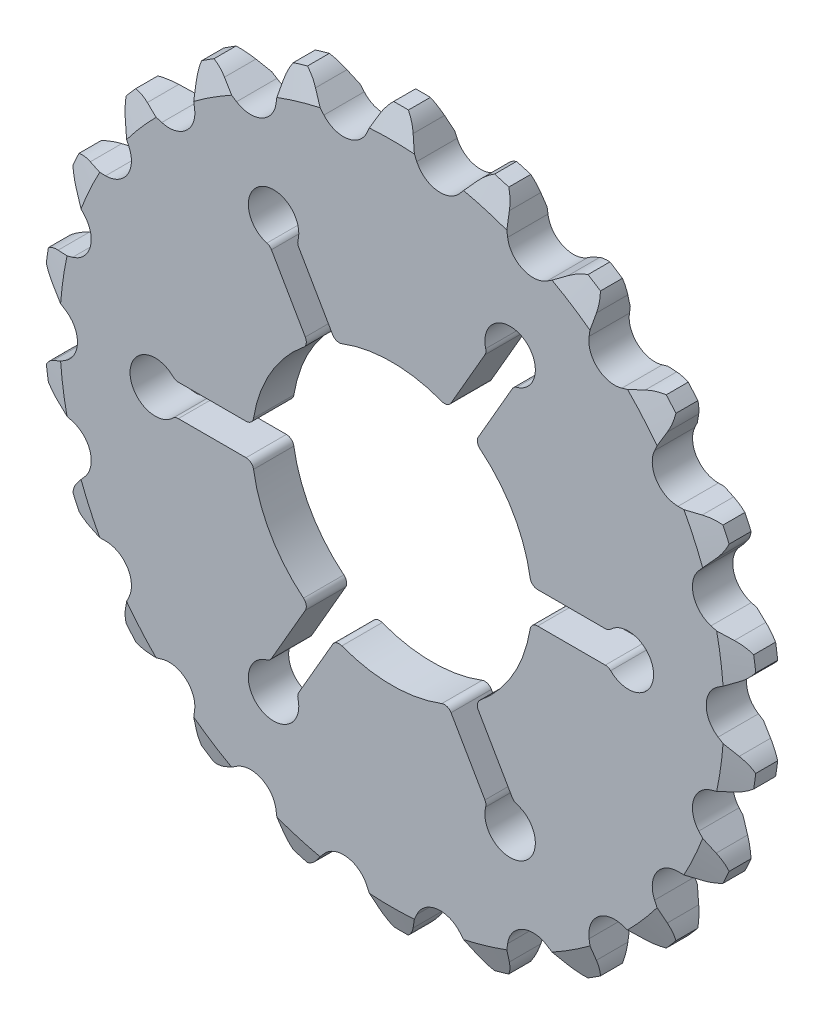
SolidWorks part; units mm, degrees
material "6063-T6"
ref_plane "Front Plane" through (0, 0, 0) normal (0, 0, 1) x (1, 0, 0)
ref_plane "Top Plane" through (0, 0, 0) normal (0, 1, 0) x (1, 0, 0)
ref_plane "Right Plane" through (0, 0, 0) normal (1, 0, 0) x (0, 0, -1)
sketch "Sketch1" plane through (0, 0, 0) normal (0, 0, 1) x (1, 0, 0)
  circle A0 centre (0, 0) radius 35.98
  dimension "D1" = 71.96
extrude "Extrude1" add sketch "Sketch1" along normal mid plane 4.06
chamfer "Chamfer1" distance 2.54 angle 20 1 edges at (35.98, 0, -2.03) first distance on face at (35.98, 0, -2.03)
chamfer "Chamfer2" distance 2.54 angle 20 1 edges at (35.98, 0, 2.03) first distance on face at (35.98, 0, 2.03)
sketch "Sketch3" plane through (0, 0, 0) normal (0, 0, -1) x (-1, 0, 0)
  line L0 (0, 0) -> (0, 39.1516) construction
  line L1 (2.5125, 32.8236) -> (1.6946, 34.6311)
  line L2 (0, 0) -> (4.8729, 33.8916) construction
  line L3 (6.8368, 32.2018) -> (8.1308, 33.7058)
  arc A0 (8.1308, 33.7058) -> (9.4203, 34.7249) centre (11.404, 30.8895) cw
  arc A1 (1.6946, 34.6311) -> (0.7444, 35.9723) centre (-2.2395, 32.8511) ccw
  arc A2 (2.5125, 32.8236) -> (6.8368, 32.2018) centre (4.8729, 33.8916) ccw
  circle A4 centre (0, 0) radius 35.98 construction
  arc A5 (9.4203, 34.7249) -> (0.7444, 35.9723) centre (0, 0) ccw
  dimension "D1" = 2.5908
  dimension "D4" = 4.318
  dimension "D9" = 2.2395
  dimension "D2" = 8.182
  dimension "D3" = 24.345
  dimension "D6" = 3.3891
  dimension "D7" = 5.0249
  dimension "D8" = 4.8729
extrude "Extrude2" cut sketch "Sketch3" against normal through all and the other way through all
ref_axis "Axis1" through (0, 0, 1.1055) along (0, 0, -1)
pattern_circular "CirPattern1" count 22 over 360 about axis through (0, 0, 1.1055) along (0, 0, -1) of "Extrude2"
sketch "Sketch4" plane through (0, 0, -2.03) normal (0, 0, -1) x (-1, 0, 0)
  circle A0 centre (0, 0) radius 14.1
  dimension "D1" = 28.2
extrude "Extrude3" cut sketch "Sketch4" against normal up to next
sketch "Sketch5" plane through (0, 0, -2.03) normal (0, 0, -1) x (-1, 0, 0)
  line L0 (12.2897, 18.1113) -> (8.2811, 11.1682)
  line L1 (5.5314, 12.7557) -> (9.54, 19.6988)
  line L2 (0, 0) -> (0, 22.3376) construction
  line L3 (11.9062, 20.6222) -> (0, 0) construction
  line L4 (8.2811, 11.1682) -> (5.5314, 12.7557)
  arc A3 (12.2897, 18.1113) -> (9.54, 19.6988) centre (11.9062, 20.6222) ccw
  dimension "D1" = 2.54
  dimension "D2" = 10
  dimension "D3" = 30
  dimension "D4" = 3.175
  dimension "D5" = 23.8125
extrude "Extrude4" cut sketch "Sketch5" against normal up to next
fillet "Fillet1" radius 0.762 4 edges at (-12.2897, 18.1113, 0) (-8.38, 11.3396, 0) (-5.6304, 12.9271, 0) (-9.54, 19.6988, 0)
pattern_circular "CirPattern6" count 6 over 360 about axis through (0, 0, 1.1055) along (0, 0, -1) of "Fillet1", "Extrude4"
ref_axis "Axis2" through (0, 0, 2.03) along (0, 0, -1)
sketch "Sketch6" plane through (0, 0, -0.0662) normal (0, 0, 1) x (1, 0, 0)
  circle A0 centre (0, 0) radius 33.44
